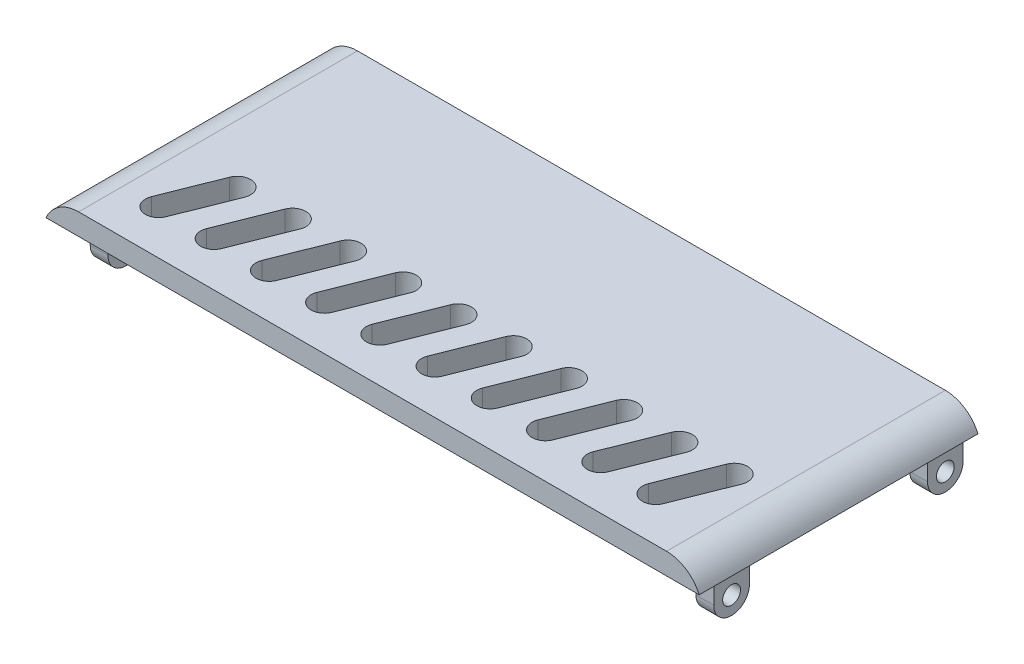
SolidWorks part; units mm, degrees
ref_plane "前视基准面" through (0, 0, 0) normal (0, 0, 1) x (1, 0, 0)
ref_plane "上视基准面" through (0, 0, 0) normal (0, 1, 0) x (1, 0, 0)
ref_plane "右视基准面" through (0, 0, 0) normal (1, 0, 0) x (0, 0, -1)
sketch "草图2" plane through (0, 0, 0) normal (0, 1, 0) x (1, 0, 0)
  line L0 (-27.0872, -11.4596) -> (-30.7532, -11.4596) construction
  line L1 (-31.0872, 19.8404) -> (42.9128, 19.8404)
  line L2 (-31.0872, 19.8404) -> (-31.0872, -11.4596)
  line L3 (-31.0872, -11.4596) -> (42.9128, -11.4596)
  line L4 (42.9128, 19.8404) -> (42.9128, -11.4596)
  dimension "D1" = 74
  dimension "D2" = 31.3
extrude "凸台-拉伸1" add sketch "草图2" along normal blind 4
fillet "圆角1" radius 4 2 edges at (-31.0872, 4, -4.1904) (42.9128, 4, -4.1904)
sketch "草图3" plane through (0, 0, -19.8404) normal (0, 0, -1) x (-1, 0, 0)
  line L1 (31.0872, 0) -> (-42.9128, 0)
  line L2 (31.0872, 0) -> (31.0872, 1.6)
  line L3 (31.0872, 1.6) -> (-42.9128, 1.6)
  line L4 (-42.9128, 0) -> (-42.9128, 1.6)
  dimension "D1" = 1.6
extrude "切除-拉伸1" cut sketch "草图3" against normal through all
sketch "草图19" plane through (0, 4, 0) normal (0, 1, 0) x (1, 0, 0)
  line L0 (-20.5872, -0.1596) -> (-23.0872, -6.4596) construction
  line L5 (-19.1929, -0.7128) -> (-21.6929, -7.0128)
  line L8 (-21.9814, 0.3937) -> (-24.4814, -5.9063)
  line L11 (38.9128, 19.8404) -> (-27.0872, 19.8404) construction
  line L14 (-27.0872, -11.4596) -> (38.9128, -11.4596) construction
  line L17 (-14.3872, -0.1596) -> (-16.8872, -6.4596) construction
  line L20 (-12.9929, -0.7128) -> (-15.4929, -7.0128)
  line L23 (-15.7814, 0.3937) -> (-18.2814, -5.9063)
  line L26 (-40.9597, 4.1904) -> (-18.0872, 4.1904) construction
  line L27 (-27.0872, 19.8404) -> (-27.0872, -11.4596) construction
  line L28 (-8.1872, -0.1596) -> (-10.6872, -6.4596) construction
  line L31 (-6.7929, -0.7128) -> (-9.2929, -7.0128)
  line L34 (-9.5814, 0.3937) -> (-12.0814, -5.9063)
  line L37 (-1.9872, -0.1596) -> (-4.4872, -6.4596) construction
  line L40 (-0.5929, -0.7128) -> (-3.0929, -7.0128)
  line L43 (-3.3814, 0.3937) -> (-5.8814, -5.9063)
  line L46 (4.2128, -0.1596) -> (1.7128, -6.4596) construction
  line L49 (5.6071, -0.7128) -> (3.1071, -7.0128)
  line L52 (2.8186, 0.3937) -> (0.3186, -5.9063)
  line L53 (10.4128, -0.1596) -> (7.9128, -6.4596) construction
  line L54 (11.8071, -0.7128) -> (9.3071, -7.0128)
  line L55 (9.0186, 0.3937) -> (6.5186, -5.9063)
  line L56 (16.6128, -0.1596) -> (14.1128, -6.4596) construction
  line L57 (18.0071, -0.7128) -> (15.5071, -7.0128)
  line L58 (15.2186, 0.3937) -> (12.7186, -5.9063)
  line L59 (22.8128, -0.1596) -> (20.3128, -6.4596) construction
  line L60 (24.2071, -0.7128) -> (21.7071, -7.0128)
  line L61 (21.4186, 0.3937) -> (18.9186, -5.9063)
  line L62 (29.0128, -0.1596) -> (26.5128, -6.4596) construction
  line L63 (30.4071, -0.7128) -> (27.9071, -7.0128)
  line L64 (27.6186, 0.3937) -> (25.1186, -5.9063)
  line L65 (35.2128, -0.1596) -> (32.7128, -6.4596) construction
  line L66 (36.6071, -0.7128) -> (34.1071, -7.0128)
  line L67 (33.8186, 0.3937) -> (31.3186, -5.9063)
  arc A32 (-19.1929, -0.7128) -> (-21.9814, 0.3937) centre (-20.5872, -0.1596) ccw
  arc A33 (-24.4814, -5.9063) -> (-21.6929, -7.0128) centre (-23.0872, -6.4596) ccw
  arc A34 (-12.9929, -0.7128) -> (-15.7814, 0.3937) centre (-14.3872, -0.1596) ccw
  arc A35 (-18.2814, -5.9063) -> (-15.4929, -7.0128) centre (-16.8872, -6.4596) ccw
  arc A36 (-6.7929, -0.7128) -> (-9.5814, 0.3937) centre (-8.1872, -0.1596) ccw
  arc A37 (-12.0814, -5.9063) -> (-9.2929, -7.0128) centre (-10.6872, -6.4596) ccw
  arc A38 (-0.5929, -0.7128) -> (-3.3814, 0.3937) centre (-1.9872, -0.1596) ccw
  arc A39 (-5.8814, -5.9063) -> (-3.0929, -7.0128) centre (-4.4872, -6.4596) ccw
  arc A40 (5.6071, -0.7128) -> (2.8186, 0.3937) centre (4.2128, -0.1596) ccw
  arc A41 (0.3186, -5.9063) -> (3.1071, -7.0128) centre (1.7128, -6.4596) ccw
  arc A42 (11.8071, -0.7128) -> (9.0186, 0.3937) centre (10.4128, -0.1596) ccw
  arc A43 (6.5186, -5.9063) -> (9.3071, -7.0128) centre (7.9128, -6.4596) ccw
  arc A44 (18.0071, -0.7128) -> (15.2186, 0.3937) centre (16.6128, -0.1596) ccw
  arc A45 (12.7186, -5.9063) -> (15.5071, -7.0128) centre (14.1128, -6.4596) ccw
  arc A46 (24.2071, -0.7128) -> (21.4186, 0.3937) centre (22.8128, -0.1596) ccw
  arc A47 (18.9186, -5.9063) -> (21.7071, -7.0128) centre (20.3128, -6.4596) ccw
  arc A48 (30.4071, -0.7128) -> (27.6186, 0.3937) centre (29.0128, -0.1596) ccw
  arc A49 (25.1186, -5.9063) -> (27.9071, -7.0128) centre (26.5128, -6.4596) ccw
  arc A50 (36.6071, -0.7128) -> (33.8186, 0.3937) centre (35.2128, -0.1596) ccw
  arc A51 (31.3186, -5.9063) -> (34.1071, -7.0128) centre (32.7128, -6.4596) ccw
  point P2 (-21.8372, -3.3096)
  point P15 (-15.6372, -3.3096)
  point P22 (-9.4372, -3.3096)
  point P29 (-3.2372, -3.3096)
  point P36 (2.9628, -3.3096)
  point P43 (9.1628, -3.3096)
  point P50 (15.3628, -3.3096)
  point P57 (21.5628, -3.3096)
  point P64 (-27.0872, 4.1904)
  point P68 (27.7628, -3.3096)
  point P75 (33.9628, -3.3096)
  dimension "D6" = 4
  dimension "D3" = 1.5
  dimension "D1" = 20
  dimension "D2" = 5
  dimension "D4" = 6.5
  dimension "D5" = 10
extrude "切除-拉伸6" cut sketch "草图19" against normal up to next
sketch "草图22" plane through (0, 1.6, 0) normal (0, -1, 0) x (1, 0, 0)
  line L0 (-30.7532, 11.4596) -> (42.5789, 11.4596) construction
  line L1 (-29.0872, 8.1596) -> (-27.0872, 8.1596)
  line L2 (-29.0872, 8.1596) -> (-29.0872, 4.1596)
  line L3 (-29.0872, 4.1596) -> (-27.0872, 4.1596)
  line L4 (-27.0872, 8.1596) -> (-27.0872, 4.1596)
  line L5 (-29.0872, 11.4596) -> (-29.0872, 1.1198) construction
  line L6 (-30.7532, -19.8404) -> (42.5789, -19.8404) construction
  line L7 (-27.0872, -19.8404) -> (-29.0872, -19.8404)
  line L8 (-27.0872, -19.8404) -> (-27.0872, -15.8404)
  line L9 (-27.0872, -15.8404) -> (-29.0872, -15.8404)
  line L10 (-29.0872, -19.8404) -> (-29.0872, -15.8404)
  line L11 (-29.0872, -5.8802) -> (-29.0872, -19.8404) construction
  line L12 (40.9128, 1.1198) -> (40.9128, 11.4596) construction
  line L13 (40.9128, 8.1596) -> (38.9128, 8.1596)
  line L14 (40.9128, 8.1596) -> (40.9128, 4.1596)
  line L15 (40.9128, 4.1596) -> (38.9128, 4.1596)
  line L16 (38.9128, 8.1596) -> (38.9128, 4.1596)
  line L18 (40.9128, -19.8404) -> (38.9128, -19.8404)
  line L19 (40.9128, -19.8404) -> (40.9128, -15.8404)
  line L20 (40.9128, -15.8404) -> (38.9128, -15.8404)
  line L21 (38.9128, -19.8404) -> (38.9128, -15.8404)
  point P26 (0, 0)
  point P27 (-29.0872, 9.9127)
  point P28 (0, 0)
  point P29 (0, 0)
  point P30 (0, 0)
  dimension "D1" = 2
  dimension "D2" = 4
  dimension "D3" = 4
  dimension "D4" = 2
  dimension "D5" = 3.3
extrude "凸台-拉伸9" add sketch "草图22" along normal blind 5.5
fillet "圆角3" radius 2 8 edges at (-28.0872, -3.9, -19.8404) (-28.0872, -3.9, -15.8404) (-28.0872, -3.9, 4.1596) (-28.0872, -3.9, 8.1596) (39.9128, -3.9, -19.8404) (39.9128, -3.9, -15.8404) (39.9128, -3.9, 4.1596) (39.9128, -3.9, 8.1596)
sketch "草图23" plane through (-29.0872, 0, 0) normal (-1, 0, 0) x (0, 0, 1)
  circle A0 centre (6.1596, -1.9) radius 1
  circle A1 centre (-17.8404, -1.9) radius 1
  arc A2 (-17.8404, -3.9) -> (-15.8404, -1.9) centre (-17.8404, -1.9) ccw construction
  arc A3 (6.1596, -3.9) -> (8.1596, -1.9) centre (6.1596, -1.9) ccw construction
  dimension "D1" = 2
  dimension "D2" = 2
extrude "切除-拉伸9" cut sketch "草图23" against normal blind 2 draft 4
sketch "草图24" plane through (0, 1.6, 0) normal (0, -1, 0) x (1, 0, 0)
  line L0 (-30.7532, 11.4596) -> (42.5789, 11.4596) construction
  line L1 (-18.7532, 10.0596) -> (-14.7532, 10.0596)
  line L2 (-18.7532, 10.0596) -> (-18.7532, 8.0596)
  line L3 (-18.7532, 8.0596) -> (-14.7532, 8.0596)
  line L4 (-14.7532, 10.0596) -> (-14.7532, 8.0596)
  line L5 (30.5789, 8.0596) -> (26.5789, 8.0596)
  line L6 (30.5789, 8.0596) -> (30.5789, 10.0596)
  line L7 (30.5789, 10.0596) -> (26.5789, 10.0596)
  line L8 (26.5789, 8.0596) -> (26.5789, 10.0596)
  line L9 (42.5789, -19.8404) -> (42.5789, 11.4596) construction
  line L10 (-30.7532, 11.4596) -> (-30.7532, -19.8404) construction
  dimension "D1" = 3.4
  dimension "D2" = 2
  dimension "D3" = 12
  dimension "D4" = 4
  dimension "D5" = 12
  dimension "D6" = 4
extrude "凸台-拉伸10" add sketch "草图24" along normal blind 0.2
sketch "草图25" plane through (0, 1.6, 0) normal (0, -1, 0) x (1, 0, 0)
  text T0 "WHISPLAY" font "@Adobe Gothic Std B" height 3.5
extrude "切除-拉伸10" cut sketch "草图25" against normal blind 0.4
sketch "草图26" plane through (40.9128, 0, 0) normal (1, 0, 0) x (0, 0, -1)
  circle A1 centre (17.8404, -1.9) radius 1
  circle A2 centre (17.8404, -1.9) radius 1
  circle A3 centre (-6.1596, -1.9) radius 1
  circle A4 centre (-6.1596, -1.9) radius 1
  dimension "D1" = 0
  dimension "D2" = 0
extrude "切除-拉伸11" cut sketch "草图26" against normal blind 2 draft 4
sketch "草图27" plane through (0, 1.6, 0) normal (0, -1, 0) x (1, 0, 0)
  line L0 (-30.7532, 11.4596) -> (42.5789, 11.4596) construction
  line L1 (-27.0872, 7.4732) -> (-24.1928, 7.4732)
  line L2 (-27.0872, 7.4732) -> (-27.0872, 8.1596)
  line L3 (-27.0872, 8.1596) -> (-24.1928, 8.1596)
  line L4 (-24.1928, 7.4732) -> (-24.1928, 8.1596)
  line L5 (-27.0872, 13.4596) -> (-27.0872, -21.8404) construction
  line L6 (38.9128, 7.4732) -> (33.8185, 7.4732)
  line L7 (38.9128, 7.4732) -> (38.9128, 8.1596)
  line L8 (38.9128, 8.1596) -> (33.8185, 8.1596)
  line L9 (33.8185, 7.4732) -> (33.8185, 8.1596)
  line L11 (38.9128, 8.1596) -> (38.9128, 6.1596) construction
  arc A0 (-21.6929, 7.0128) -> (-24.4814, 5.9063) centre (-23.0872, 6.4596) ccw construction
  arc A1 (34.1071, 7.0128) -> (31.3186, 5.9063) centre (32.7128, 6.4596) ccw construction
  point P5 (0, 0)
  point P7 (39.5128, 7.4596)
  point P16 (39.5128, 7.4596)
  point P21 (0, 0)
  point P24 (38.9128, 7.4732)
  point P27 (0, 0)
  point P28 (0, 0)
  dimension "D1" = 3.3
extrude "凸台-拉伸11" add sketch "草图27" along normal blind 3
chamfer "倒角1" distance 1 angle 45 2 edges at (-25.64, -1.4, 8.1596) (36.3657, -1.4, 8.1596)
